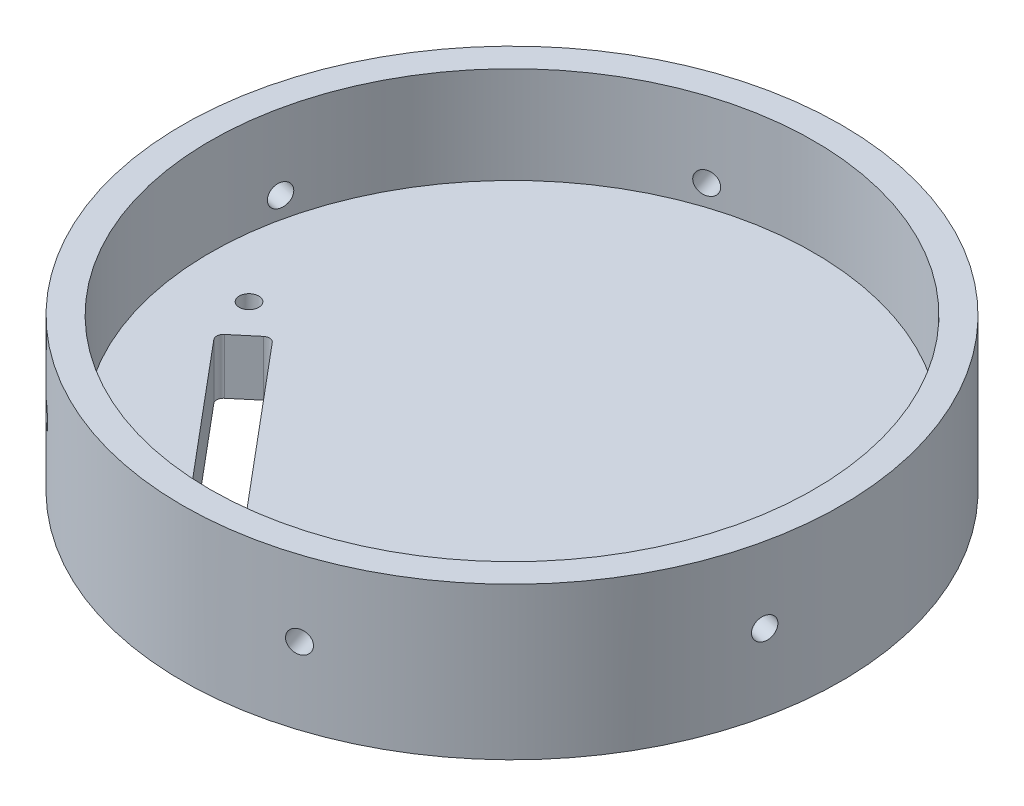
SolidWorks part; units mm, degrees
material "6061-T4 (SS)"
ref_plane "Front Plane" through (0, 0, 0) normal (0, 0, 1) x (1, 0, 0)
ref_plane "Top Plane" through (0, 0, 0) normal (0, 1, 0) x (1, 0, 0)
ref_plane "Right Plane" through (0, 0, 0) normal (1, 0, 0) x (0, 0, -1)
sketch "Sketch1" plane through (0, 0, 0) normal (0, 1, 0) x (1, 0, 0)
  circle A0 centre (0, 0) radius 75.692
  circle A1 centre (0, 0) radius 69.342
  dimension "D1" = 151.384
  dimension "D2" = 138.684
extrude "Boss-Extrude1" add sketch "Sketch1" along normal blind 22.225
sketch "Sketch2" plane through (0, 0, 0) normal (0, -1, 0) x (1, 0, 0)
  circle A0 centre (0, 0) radius 75.692
  dimension "D1" = 151.384
extrude "Boss-Extrude2" add sketch "Sketch2" along normal blind 12.7
hole_wizard "Tap Drill for 1/4-20 Tap1" positions "3DSketch2" profile "Sketch4" hole size "1/4-20" standard "ANSI Inch"
sketch3d "3DSketch2"
  line L0 (73.6526, 22.225, 17.4519) -> (73.9972, 4.8963, 15.9279)
  circle A1 centre (0, 22.225, 0) radius 75.692 construction
  point P0 (73.9972, 4.8963, 15.9279)
  point P10 (0, 97.917, 0)
  point P12 (-133.403, 50.4262, 0)
  dimension "D1" = 17.399
sketch "Sketch4" plane through (73.9972, 4.8963, 15.9279) normal (0, 1, 0) x (0.2104, 0, -0.9776)
  line L0 (0, 0) -> (0, 11.1858)
  line L1 (0, 11.1858) -> (2.5527, 9.652)
  line L2 (2.5527, 9.652) -> (2.5527, 0)
  line L5 (2.5527, 0) -> (0, 0)
  line L10 (0, 11.1858) -> (-2.5527, 9.652) construction
  line L11 (0, -6.35) -> (0, 107.95) construction
  dimension "Hole Dia." = 5.1054
  dimension "Hole Depth" = 9.652
  dimension "Drill Angle" = 118
pattern_circular "CirPattern1" count 6 over 360 about axis through (0, 22.225, 0) along (0, -1, 0) of "Tap Drill for 1/4-20 Tap1" reverse direction yes
sketch "Sketch5" plane through (0, 0, 0) normal (0, 1, 0) x (1, 0, 0)
  line L0 (0, 0) -> (0, -69.342) construction
  line L1 (-52.6502, -15.6476) -> (-45.3536, -9.525)
  line L2 (-52.6502, -15.6476) -> (-19.9966, -54.5626)
  line L3 (-19.9966, -54.5626) -> (-12.7, -48.4401)
  line L4 (-45.3536, -9.525) -> (-12.7, -48.4401)
  circle A0 centre (0, 0) radius 69.342 construction
  dimension "D1" = 40
  dimension "D2" = 9.525
  dimension "D3" = 50.8
  dimension "D4" = 12.7
  dimension "D5" = 9.525
extrude "Cut-Extrude1" cut sketch "Sketch5" against normal through all
fillet "Fillet1" radius 1.5875 4 edges at (-19.9966, -6.35, 54.5626) (-12.7, -6.35, 48.4401) (-45.3536, -6.35, 9.525) (-52.6502, -6.35, 15.6476)
ref_plane "Plane1" through (-34.953, 0, 29.3291) normal (0.766, 0, -0.6428) x (-0.6428, 0, -0.766)
sketch "Sketch6" plane through (0, 0, 0) normal (0, 1, 0) x (1, 0, 0)
  line L0 (-30.4632, -34.6799) -> (-39.4429, -23.9782) construction
  line L1 (-46.5697, -10.5454) -> (-51.4341, -14.6271) construction
  line L2 (-46.5697, -10.5454) -> (-51.4341, -14.6271)
  line L3 (-49.0019, -12.5863) -> (-55.1244, -5.2897) construction
  point P0 (-55.1244, -5.2897)
  dimension "D1" = 9.525
hole_wizard "M4 Clearance Hole1" positions "Sketch7" profile "Sketch8" hole size "M4" standard "ANSI Metric" end condition up to next
sketch "Sketch7" plane through (0, 0, 0) normal (0, 1, 0) x (1, 0, 0)
  point P0 (-55.1244, -5.2897)
sketch "Sketch8" plane through (-55.1244, 0, 5.2897) normal (1, 0, 0) x (0, 0, 1)
  line L0 (0, 0) -> (0, 12.7)
  line L1 (0, 12.7) -> (2.25, 12.7)
  line L2 (2.25, 12.7) -> (2.25, 0)
  line L5 (2.25, 0) -> (0, 0)
  line L11 (0, -6.35) -> (0, 107.95) construction
  dimension "Thru Hole Dia." = 4.5
  dimension "Thru Hole Depth" = 12.7
